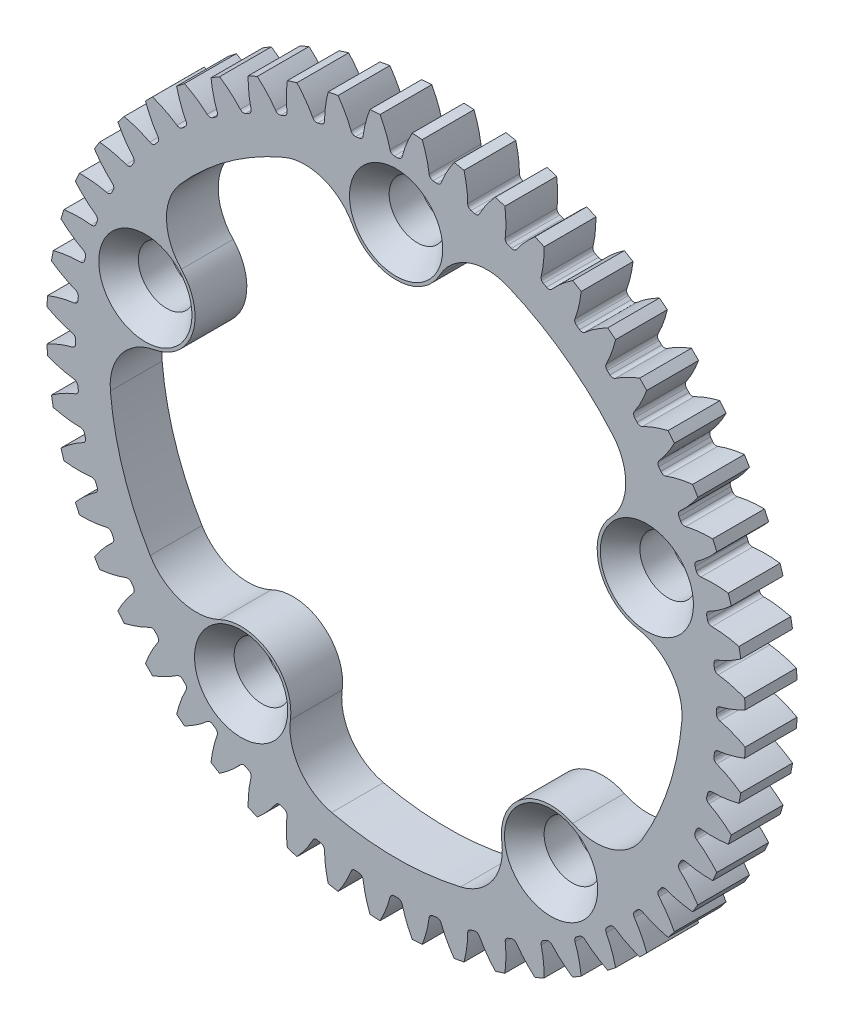
SolidWorks part; units mm, degrees
ref_plane "Front Plane" through (0, 0, 0) normal (0, 0, 1) x (1, 0, 0)
ref_plane "Top Plane" through (0, 0, 0) normal (0, 1, 0) x (1, 0, 0)
ref_plane "Right Plane" through (0, 0, 0) normal (1, 0, 0) x (0, 0, -1)
sketch "Sketch1" plane through (0, 0, 0) normal (0, 0, 1) x (1, 0, 0)
  circle A0 centre (0, 0) radius 21.4312
  dimension "D1" = 42.8625
extrude "Boss-Extrude1" add sketch "Sketch1" against normal blind 3.175
sketch "Sketch2" plane through (0, 0, 0) normal (0, 0, 1) x (1, 0, 0)
  line L0 (19.3906, 0.2968) -> (19.643, 0.3006)
  line L1 (19.3906, -0.2968) -> (19.643, -0.3006)
  circle A0 centre (0, 0) radius 21.4312
  circle A1 centre (0, 0) radius 19.3929
  circle A2 centre (0, 0) radius 20.6375
  circle A3 centre (0, 0) radius 19.6453
  spline S0 degree 4 poles (19.3906, 0.2968) (19.3998, 0.2971) (19.4255, 0.2984) (19.474, 0.3027) (19.553, 0.3126) (19.6532, 0.329) (19.7821, 0.3548) (19.9331, 0.391) (20.0979, 0.4367) (20.2759, 0.493) (20.4522, 0.5548) (20.6267, 0.6217) (20.7993, 0.693) (21.0067, 0.785) (21.253, 0.9029) (21.5372, 1.0517) (21.8548, 1.2334) (22.173, 1.4321) (22.4815, 1.6388) (22.7875, 1.86) (23.0794, 2.0829) (23.3762, 2.3269) (23.647, 2.5584) (23.9428, 2.8313) (24.1793, 3.0554) (24.483, 3.3651) (24.6597, 3.5521) (24.8636, 3.7757) (24.9525, 3.8775) (25.0073, 3.9401) knots 0 0 0 0 0 0.005377 0.015084 0.028532 0.04661 0.064855 0.092111 0.119476 0.146842 0.174209 0.201575 0.228941 0.256307 0.307035 0.361767 0.4165 0.471232 0.525964 0.580697 0.635429 0.690161 0.744894 0.799626 0.854358 0.909091 0.954545 1 1 1 1 1 construction
  spline S1 degree 4 poles (19.3906, 0.2968) (19.3998, 0.2971) (19.4255, 0.2984) (19.474, 0.3027) (19.553, 0.3126) (19.6532, 0.329) (19.7821, 0.3548) (19.9331, 0.391) (20.0979, 0.4367) (20.2759, 0.493) (20.4522, 0.5548) (20.6267, 0.6217) (20.7993, 0.693) (21.0067, 0.785) (21.253, 0.9029) (21.5372, 1.0517) (21.8548, 1.2334) (22.173, 1.4321) (22.4815, 1.6388) (22.7875, 1.86) (23.0794, 2.0829) (23.3762, 2.3269) (23.647, 2.5584) (23.9428, 2.8313) (24.1793, 3.0554) (24.4171, 3.2979) (24.5319, 3.4176) (24.5901, 3.4794) knots 0 0 0 0 0 0.005377 0.015084 0.028532 0.04661 0.064855 0.092111 0.119476 0.146842 0.174209 0.201575 0.228941 0.256307 0.307035 0.361767 0.4165 0.471232 0.525964 0.580697 0.635429 0.690161 0.744894 0.799626 0.854358 0.909091 0.909091 0.909091 0.909091 0.909091
  spline S2 degree 4 poles (19.3906, -0.2968) (19.3998, -0.2971) (19.4255, -0.2984) (19.474, -0.3027) (19.553, -0.3126) (19.6532, -0.329) (19.7821, -0.3548) (19.9331, -0.391) (20.0979, -0.4367) (20.2759, -0.493) (20.4522, -0.5548) (20.6267, -0.6217) (20.7993, -0.693) (21.0067, -0.785) (21.253, -0.9029) (21.5372, -1.0517) (21.8548, -1.2334) (22.173, -1.4321) (22.4815, -1.6388) (22.7875, -1.86) (23.0794, -2.0829) (23.3762, -2.3269) (23.647, -2.5584) (23.9428, -2.8313) (24.1793, -3.0554) (24.483, -3.3651) (24.6597, -3.5521) (24.8636, -3.7757) (24.9525, -3.8775) (25.0073, -3.9401) knots 0 0 0 0 0 0.005377 0.015084 0.028532 0.04661 0.064855 0.092111 0.119476 0.146842 0.174209 0.201575 0.228941 0.256307 0.307035 0.361767 0.4165 0.471232 0.525964 0.580697 0.635429 0.690161 0.744894 0.799626 0.854358 0.909091 0.954545 1 1 1 1 1 construction
  spline S3 degree 4 poles (19.3906, -0.2968) (19.3998, -0.2971) (19.4255, -0.2984) (19.474, -0.3027) (19.553, -0.3126) (19.6532, -0.329) (19.7821, -0.3548) (19.9331, -0.391) (20.0979, -0.4367) (20.2759, -0.493) (20.4522, -0.5548) (20.6267, -0.6217) (20.7993, -0.693) (21.0067, -0.785) (21.253, -0.9029) (21.5372, -1.0517) (21.8548, -1.2334) (22.173, -1.4321) (22.4815, -1.6388) (22.7875, -1.86) (23.0794, -2.0829) (23.3762, -2.3269) (23.647, -2.5584) (23.9428, -2.8313) (24.1793, -3.0554) (24.4171, -3.2979) (24.5319, -3.4176) (24.5901, -3.4794) knots 0 0 0 0 0 0.005377 0.015084 0.028532 0.04661 0.064855 0.092111 0.119476 0.146842 0.174209 0.201575 0.228941 0.256307 0.307035 0.361767 0.4165 0.471232 0.525964 0.580697 0.635429 0.690161 0.744894 0.799626 0.854358 0.909091 0.909091 0.909091 0.909091 0.909091
  dimension "D2" = 38.7858
  dimension "D3" = 42.8625
  dimension "D4" = 41.275
  dimension "D1" = 39.2906
extrude "Cut-Extrude1" cut sketch "Sketch2" against normal up to next contours A2 S3 A0 S1 | A3 S3 A2 S1 region at (20.1932, 0, 0) region at (21.0592, 0, 0)
fillet "Fillet1" radius 0.2663 2 edges at (19.6426, -0.328, -1.5875) (19.6426, 0.328, -1.5875)
pattern_circular "CirPattern1" count 52 over 360 about axis through (0, 0, 0) along (0, 0, 1) of "Cut-Extrude1", "Fillet1"
sketch "Sketch4" plane through (0, 0, 0) normal (0, 0, 1) x (1, 0, 0)
  arc A1 (15.0804, -9.0538) -> (17.522, -1.5393) centre (0, 0) ccw
  arc A2 (17.522, -1.5393) -> (14.8271, 1.9977) centre (14.2327, -1.2503) ccw
  arc A3 (13.1696, 7.099) -> (14.8271, 1.9977) centre (15.3758, 4.9959) ccw
  arc A4 (13.1696, 7.099) -> (13.2708, 11.5445) centre (10.7795, 9.3773) ccw
  arc A5 (13.2708, 11.5445) -> (6.8786, 16.1888) centre (0, 0) ccw
  arc A6 (6.8786, 16.1888) -> (2.6819, 14.7188) centre (5.5873, 13.1497) ccw
  arc A7 (-2.6819, 14.7188) -> (2.6819, 14.7188) centre (0, 16.1671) ccw
  arc A8 (-2.6819, 14.7188) -> (-6.8786, 16.1888) centre (-5.5873, 13.1497) ccw
  arc A9 (-6.8786, 16.1888) -> (-13.2708, 11.5445) centre (0, 0) ccw
  arc A10 (-13.2708, 11.5445) -> (-13.1696, 7.099) centre (-10.7795, 9.3773) ccw
  arc A11 (-14.8271, 1.9977) -> (-13.1696, 7.099) centre (-15.3758, 4.9959) ccw
  arc A12 (-14.8271, 1.9977) -> (-17.522, -1.5393) centre (-14.2327, -1.2503) ccw
  arc A13 (-17.522, -1.5393) -> (-15.0804, -9.0538) centre (0, 0) ccw
  arc A14 (-15.0804, -9.0538) -> (-10.8212, -10.3313) centre (-12.2494, -7.3542) ccw
  arc A15 (-6.4818, -13.4841) -> (-10.8212, -10.3313) centre (-9.5028, -13.0795) ccw
  arc A16 (-6.4818, -13.4841) -> (-3.9506, -17.1401) centre (-3.209, -13.9225) ccw
  arc A17 (-3.9506, -17.1401) -> (3.9506, -17.1401) centre (0, 0) ccw
  arc A18 (3.9506, -17.1401) -> (6.4818, -13.4841) centre (3.209, -13.9225) ccw
  arc A19 (10.8212, -10.3313) -> (6.4818, -13.4841) centre (9.5028, -13.0795) ccw
  arc A20 (10.8212, -10.3313) -> (15.0804, -9.0538) centre (12.2494, -7.3542) ccw
  arc A21 (14.9715, -8.9885) -> (17.3955, -1.5282) centre (0, 0) ccw
  arc A22 (17.3955, -1.5282) -> (14.8043, 1.8728) centre (14.2327, -1.2503) ccw
  arc A23 (13.0777, 7.1866) -> (14.8043, 1.8728) centre (15.3758, 4.9959) ccw
  arc A24 (13.0777, 7.1866) -> (13.175, 11.4612) centre (10.7795, 9.3773) ccw
  arc A25 (13.175, 11.4612) -> (6.8289, 16.0719) centre (0, 0) ccw
  arc A26 (6.8289, 16.0719) -> (2.7936, 14.6584) centre (5.5873, 13.1497) ccw
  arc A27 (-2.7936, 14.6584) -> (2.7936, 14.6584) centre (0, 16.1671) ccw
  arc A28 (-2.7936, 14.6584) -> (-6.8289, 16.0719) centre (-5.5873, 13.1497) ccw
  arc A29 (-6.8289, 16.0719) -> (-13.175, 11.4612) centre (0, 0) ccw
  arc A30 (-13.175, 11.4612) -> (-13.0777, 7.1866) centre (-10.7795, 9.3773) ccw
  arc A31 (-14.8043, 1.8728) -> (-13.0777, 7.1866) centre (-15.3758, 4.9959) ccw
  arc A32 (-14.8043, 1.8728) -> (-17.3955, -1.5282) centre (-14.2327, -1.2503) ccw
  arc A33 (-17.3955, -1.5282) -> (-14.9715, -8.9885) centre (0, 0) ccw
  arc A34 (-14.9715, -8.9885) -> (-10.8761, -10.2168) centre (-12.2494, -7.3542) ccw
  arc A35 (-6.3559, -13.501) -> (-10.8761, -10.2168) centre (-9.5028, -13.0795) ccw
  arc A36 (-6.3559, -13.501) -> (-3.9221, -17.0163) centre (-3.209, -13.9225) ccw
  arc A37 (-3.9221, -17.0163) -> (3.9221, -17.0163) centre (0, 0) ccw
  arc A38 (3.9221, -17.0163) -> (6.3559, -13.501) centre (3.209, -13.9225) ccw
  arc A39 (10.8761, -10.2168) -> (6.3559, -13.501) centre (9.5028, -13.0795) ccw
  arc A40 (10.8761, -10.2168) -> (14.9715, -8.9885) centre (12.2494, -7.3542) ccw
  arc A41 (14.9715, -8.9885) -> (17.3955, -1.5282) centre (0, 0) ccw construction
  arc A42 (17.3955, -1.5282) -> (14.8043, 1.8728) centre (14.2327, -1.2503) ccw construction
  arc A43 (13.0777, 7.1866) -> (14.8043, 1.8728) centre (15.3758, 4.9959) ccw construction
  arc A44 (13.0777, 7.1866) -> (13.175, 11.4612) centre (10.7795, 9.3773) ccw construction
  arc A45 (13.175, 11.4612) -> (6.8289, 16.0719) centre (0, 0) ccw construction
  arc A46 (6.8289, 16.0719) -> (2.7936, 14.6584) centre (5.5873, 13.1497) ccw construction
  arc A47 (-2.7936, 14.6584) -> (2.7936, 14.6584) centre (0, 16.1671) ccw construction
  arc A48 (-2.7936, 14.6584) -> (-6.8289, 16.0719) centre (-5.5873, 13.1497) ccw construction
  arc A49 (-6.8289, 16.0719) -> (-13.175, 11.4612) centre (0, 0) ccw construction
  arc A50 (-13.175, 11.4612) -> (-13.0777, 7.1866) centre (-10.7795, 9.3773) ccw construction
  arc A51 (-14.8043, 1.8728) -> (-13.0777, 7.1866) centre (-15.3758, 4.9959) ccw construction
  arc A52 (-14.8043, 1.8728) -> (-17.3955, -1.5282) centre (-14.2327, -1.2503) ccw construction
  arc A53 (-17.3955, -1.5282) -> (-14.9715, -8.9885) centre (0, 0) ccw construction
  arc A54 (-14.9715, -8.9885) -> (-10.8761, -10.2168) centre (-12.2494, -7.3542) ccw construction
  arc A55 (-6.3559, -13.501) -> (-10.8761, -10.2168) centre (-9.5028, -13.0795) ccw construction
  arc A56 (-6.3559, -13.501) -> (-3.9221, -17.0163) centre (-3.209, -13.9225) ccw construction
  arc A57 (-3.9221, -17.0163) -> (3.9221, -17.0163) centre (0, 0) ccw construction
  arc A58 (3.9221, -17.0163) -> (6.3559, -13.501) centre (3.209, -13.9225) ccw construction
  arc A59 (10.8761, -10.2168) -> (6.3559, -13.501) centre (9.5028, -13.0795) ccw construction
  arc A60 (10.8761, -10.2168) -> (14.9715, -8.9885) centre (12.2494, -7.3542) ccw construction
  dimension "D1" = 0
  dimension "D2" = 0.127
extrude "Cut-Extrude2" cut sketch "Sketch4" against normal up to next
hole_wizard "CSK for #4 Flat Head Machine Screw1" positions "Sketch5" profile "Sketch7" countersink size "#4" standard "ANSI Inch" end condition up to next
sketch "Sketch5" plane through (0, 0, 0) normal (0, 0, 1) x (1, 0, 0)
  point P0 (0, 16.1671)
  point P3 (15.3758, 4.9959)
  point P6 (9.5028, -13.0795)
  point P9 (-9.5028, -13.0795)
  point P12 (-15.3758, 4.9959)
sketch "Sketch7" plane through (0, 16.1671, 0) normal (1, 0, 0) x (0, -1, 0)
  line L0 (0, 0) -> (0, 3.175)
  line L1 (0, 3.175) -> (1.7272, 3.175)
  line L2 (1.7272, 3.175) -> (1.7272, 1.3003)
  line L3 (1.7272, 1.3003) -> (2.8575, 0)
  line L5 (2.8575, 0) -> (0, 0)
  line L6 (-1.7272, 1.3003) -> (-2.8575, 0) construction
  line L11 (0, -6.35) -> (0, 107.95) construction
  dimension "Thru Hole Dia." = 3.4544
  dimension "Thru Hole Depth" = 3.175
  dimension "Near C'Sink Dia." = 5.715
  dimension "Near C'Sink Angle" = 82
equation "\"Module\"= .9143'module = 25.4/PD"
equation "\"DiametralPitch\"= 32'DP=25.4/module"
equation "\"NumTeeth\"= 52"
equation "\"PressureAngle\"= 20"
equation "\"Addendum\"= 1 / \"DiametralPitch\""
equation "\"Dedendum\"= 1.25 / \"DiametralPitch\""
equation "\"WorkingDepth\"= 2 / \"DiametralPitch\""
equation "\"WholeDepth\"= 2.25 / \"DiametralPitch\""
equation "\"Clearance\"= 0.25 / \"DiametralPitch\""
equation "\"ToothThickness\"= 1.5708 / \"DiametralPitch\""
equation "\"CircularPitch\"= pi / \"DiametralPitch\""
equation "\"PitchCircle\"= \"NumTeeth\" / \"DiametralPitch\""
equation "\"OutsideDiameter\"= ( \"NumTeeth\" + 2 ) / \"DiametralPitch\""
equation "\"Fillet\"= \"Clearance\" * cos ( \"PressureAngle\" ) * tan ( ( 90 + \"PressureAngle\" ) / 2 )"
equation "\"AddendumCircle\"= \"PitchCircle\" + ( 2 * \"Addendum\" )"
equation "\"DedendumCircle\"= \"PitchCircle\" - ( 2 * \"Dedendum\" )"
equation "\"BaseCircle\"= \"PitchCircle\" * cos ( \"PressureAngle\" )"
equation "\"PitchAngle\"= 360deg / \"NumTeeth\""
equation "\"Alpha\"= sqr ( \"PitchCircle\" ^ 2 - \"BaseCircle\" ^ 2 ) / \"BaseCircle\" * 180 / PI - \"PressureAngle\""
equation "\"Beta\"= ( \"PitchAngle\" / 4 - \"Alpha\" )"
equation "\"Phi\"= sqr ( ( \"AddendumCircle\" / 2 ) ^ 2 - ( \"BaseCircle\" / 2 ) ^ 2 ) / ( \"BaseCircle\" / 2 )"
equation "\"D1@Sketch1\"=\"OutsideDiameter\""
equation "\"D2@Sketch2\"=\"BaseCircle\""
equation "\"D3@Sketch2\"=\"AddendumCircle\""
equation "\"D4@Sketch2\"=\"PitchCircle\""
equation "\"D1@CirPattern1\"=\"NumTeeth\""
equation "\"D1@Fillet1\"=\"Fillet\""
equation "\"D1@Sketch2\"=\"DedendumCircle\""
